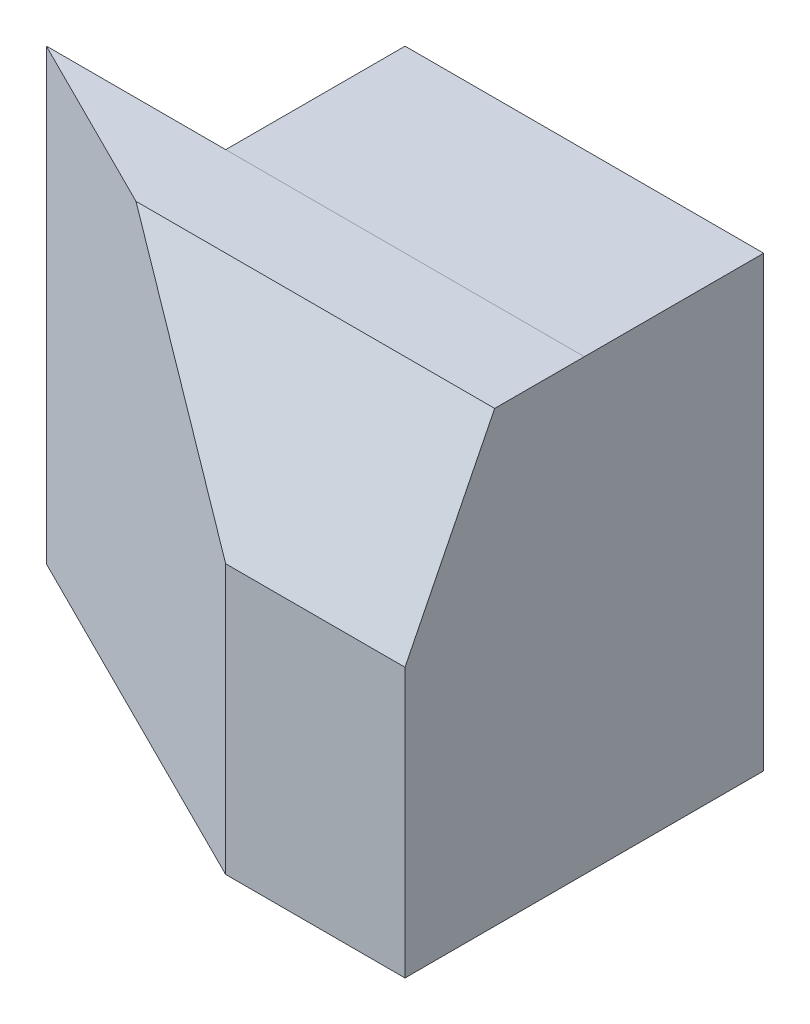
SolidWorks part; units mm, degrees
ref_plane "Front" through (0, 0, 0) normal (0, 0, 1) x (1, 0, 0)
ref_plane "Top" through (0, 0, 0) normal (0, 1, 0) x (1, 0, 0)
ref_plane "Right" through (0, 0, 0) normal (1, 0, 0) x (0, 0, -1)
sketch "Sketch1" plane through (0, 0, 0) normal (0, 0, 1) x (1, 0, 0)
  line L1 (0, 0) -> (6, 0)
  line L2 (0, 0) -> (0, 3)
  line L3 (2, 5) -> (6, 5)
  line L4 (6, 0) -> (6, 5)
  line L5 (2, 5) -> (0, 5)
  line L6 (0, 5) -> (0, 3)
  point P2 (0, 5)
  dimension "D2" = 6
extrude "Boss-Extrude1" add sketch "Sketch1" along normal blind 2
sketch "Sketch2" plane through (0, 0, 2) normal (0, 0, 1) x (1, 0, 0)
  line L1 (6, 0) -> (0, 0)
  line L2 (6, 0) -> (6, 5.0011)
  line L3 (6, 5.0011) -> (0, 5.0011)
  line L4 (0, 0) -> (0, 5.0011)
  dimension "D1" = 5.0011
  dimension "D2" = 6
extrude "Boss-Extrude2" add sketch "Sketch2" along normal blind 2
fillet "Chamfer1" radius 1 1 edges at (3, 5.0011, 4) profile chamfer first distance on face at (3.75, 5.0009, 3.5)
sketch3d "3DSketch1"
  line L0 (6, 3.0011, 4) -> (0, 3.0011, 4) construction
  line L1 (0, 0, 4) -> (6, 0, 4) construction
  line L2 (0, 5.0011, 3) -> (6, 5.0011, 3) construction
  line L3 (0, 0, 4) -> (0, 0, 0) construction
  line L6 (2, 5.0011, 3) -> (4, 3.0011, 4)
  line L7 (4, 3.0011, 4) -> (4, 0, 4)
  line L8 (4, 0, 4) -> (0, 0, 2)
  line L10 (0, 5.0011, 3) -> (0, 5.0011, 2) construction
  line L11 (2, 5.0011, 3) -> (0, 5.0011, 2)
  line L12 (0, 5.0011, 2) -> (0, 0, 2)
  point P0 (4, 3.0011, 4)
  point P1 (4, 0, 4)
  point P4 (2, 5.0011, 3)
  point P7 (0, 5.0011, 2)
  point P10 (0, 0, 2)
  dimension "D1" = 2
  dimension "D2" = 2
  dimension "D3" = 4
extrude "Cut-Extrude2" cut sketch "3DSketch1" along direction (0, 0, 1) on the side against the normal blind 2 contours L7 L8 L12 L11 L6
sketch "Sketch4" plane through (0, 0, 0) normal (0, 0, -1) x (-1, 0, 0)
  line L0 (0, 5.0005) -> (-2, 5.0011)
  line L1 (-2, 5.0011) -> (-4, 3.0011)
  line L2 (-4, 3.0011) -> (-4, 0)
  line L3 (-4, 0) -> (0, 0)
  line L4 (0, 0) -> (0, 5.0005)
extrude "Cut-Extrude3" cut sketch "Sketch4" against normal blind 2
